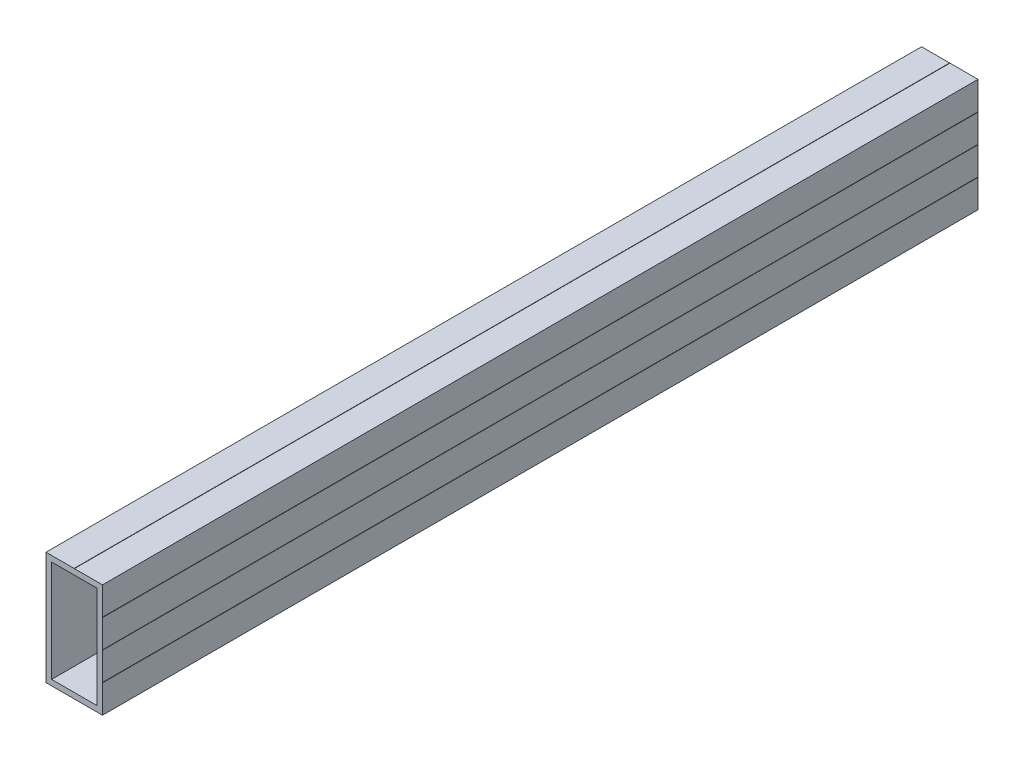
SolidWorks part; units mm, degrees
ref_plane "Front Plane" through (0, 0, 0) normal (0, 0, 1) x (1, 0, 0)
ref_plane "Top Plane" through (0, 0, 0) normal (0, 1, 0) x (1, 0, 0)
ref_plane "Right Plane" through (0, 0, 0) normal (1, 0, 0) x (0, 0, -1)
ref_plane "Plane1" through (12.7, 0, 0) normal (1, 0, 0) x (0, 0, -1)
sketch "Sketch1" plane through (12.7, 0, 0) normal (1, 0, 0) x (0, 0, -1)
  line L0 (-749.3, 25.4) -> (-749.3, -25.4)
  line L1 (-749.3, -25.4) -> (749.3, -25.4)
  line L2 (749.3, -25.4) -> (749.3, 25.4)
  line L3 (749.3, 25.4) -> (-749.3, 25.4)
extrude "Boss-Extrude1" add sketch "Sketch1" against normal blind 25.4
sketch "Sketch2" plane through (0, 0, 749.3) normal (0, 0, 1) x (1, 0, 0)
  line L0 (0.0762, 25.4) -> (-0.0762, 25.4)
  line L1 (-0.0762, 25.4) -> (0.0762, 25.2476)
  line L2 (0.0762, 25.2476) -> (0.0762, 25.4)
extrude "Cut-Extrude1" cut sketch "Sketch2" against normal blind 1498.6
sketch "Sketch3" plane through (0, 0, 749.3) normal (0, 0, 1) x (1, 0, 0)
  line L0 (12.7, 12.6238) -> (12.7, 12.7762)
  line L1 (12.7, 12.7762) -> (12.5476, 12.7762)
  line L2 (12.5476, 12.7762) -> (12.7, 12.6238)
extrude "Cut-Extrude2" cut sketch "Sketch3" against normal through all
sketch "Sketch4" plane through (0, 0, 749.3) normal (0, 0, 1) x (1, 0, 0)
  line L0 (12.7, -0.0762) -> (12.7, 0.0762)
  line L1 (12.7, 0.0762) -> (12.5476, -0.0762)
  line L2 (12.5476, -0.0762) -> (12.7, -0.0762)
extrude "Cut-Extrude3" cut sketch "Sketch4" against normal blind 1498.6
sketch "Sketch5" plane through (0, 0, 749.3) normal (0, 0, 1) x (1, 0, 0)
  line L0 (12.7, -12.7762) -> (12.7, -12.6238)
  line L1 (12.7, -12.6238) -> (12.5476, -12.6238)
  line L2 (12.5476, -12.6238) -> (12.7, -12.7762)
extrude "Cut-Extrude4" cut sketch "Sketch5" against normal blind 1498.6
sketch "Sketch6" plane through (0, 0, 749.3) normal (0, 0, 1) x (1, 0, 0)
  line L0 (0.0762, -25.4) -> (-0.0762, -25.2476)
  line L1 (-0.0762, -25.2476) -> (-0.0762, -25.4)
  line L2 (-0.0762, -25.4) -> (0.0762, -25.4)
extrude "Cut-Extrude5" cut sketch "Sketch6" against normal through all
sketch "Sketch7" plane through (0, 0, 749.3) normal (0, 0, 1) x (1, 0, 0)
  line L0 (-12.7, -12.6238) -> (-12.7, -12.7762)
  line L1 (-12.7, -12.7762) -> (-12.5476, -12.7762)
  line L2 (-12.5476, -12.7762) -> (-12.7, -12.6238)
extrude "Cut-Extrude6" cut sketch "Sketch7" against normal through all
sketch "Sketch8" plane through (0, 0, 749.3) normal (0, 0, 1) x (1, 0, 0)
  line L0 (-12.7, 0.0762) -> (-12.7, -0.0762)
  line L1 (-12.7, -0.0762) -> (-12.5476, 0.0762)
  line L2 (-12.5476, 0.0762) -> (-12.7, 0.0762)
extrude "Cut-Extrude7" cut sketch "Sketch8" against normal blind 1498.6
sketch "Sketch9" plane through (0, 0, 749.3) normal (0, 0, 1) x (1, 0, 0)
  line L0 (-12.7, 12.7762) -> (-12.7, 12.6238)
  line L1 (-12.7, 12.6238) -> (-12.5476, 12.6238)
  line L2 (-12.5476, 12.6238) -> (-12.7, 12.7762)
extrude "Cut-Extrude8" cut sketch "Sketch9" against normal blind 1498.6
sketch "Sketch10" plane through (0, 0, 749.3) normal (0, 0, 1) x (1, 0, 0)
  line L0 (10.16, -22.86) -> (10.16, 22.86)
  line L1 (10.16, 22.86) -> (-10.16, 22.86)
  line L2 (-10.16, 22.86) -> (-10.16, -22.86)
  line L3 (-10.16, -22.86) -> (10.16, -22.86)
extrude "Cut-Extrude9" cut sketch "Sketch10" against normal through all
draft "Draft1" type of draft neutral plane draft angle 45 faces to draft 1 face at (0.0762, 25.3238, 0) neutral plane through (-12.7, 25.4, -749.3) neutral plane normal (0, 1, 0) parameters "D1"=45
draft "Draft2" type of draft neutral plane draft angle 45 faces to draft 1 face at (12.6238, 12.7762, 0) neutral plane through (12.7, 0, 0) neutral plane normal (1, 0, 0) parameters "D1"=45
draft "Draft3" type of draft neutral plane draft angle 45 faces to draft 1 face at (-0.0762, -25.3238, 0) neutral plane through (-12.7, -25.4, 749.3) neutral plane normal (0, -1, 0) parameters "D1"=45
draft "Draft4" type of draft neutral plane draft angle 45 faces to draft 1 face at (-12.6238, -12.7762, 0) neutral plane through (-12.7, 0, 0) neutral plane normal (-1, 0, 0) parameters "D1"=45
draft "Draft5" type of draft neutral plane draft angle 45 faces to draft 2 face at (12.6238, -12.6238, 0) face at (12.6238, 0, 0) neutral plane through (12.7, 0, 0) neutral plane normal (1, 0, 0) parameters "D1"=45
draft "Draft6" type of draft neutral plane draft angle 45 faces to draft 2 face at (-12.6238, 0, 0) face at (-12.6238, 12.6238, 0) neutral plane through (-12.7, 0, 0) neutral plane normal (-1, 0, 0) parameters "D1"=45
sketch "Sketch11" plane through (0, 0, -749.3) normal (0, 0, -1) x (-1, 0, 0)
  line L1 (28.0564, 44.6652) -> (-33.9059, 44.6652)
  line L2 (28.0564, 44.6652) -> (28.0564, -44.0138)
  line L3 (28.0564, -44.0138) -> (-33.9059, -44.0138)
  line L4 (-33.9059, 44.6652) -> (-33.9059, -44.0138)
extrude "Cut-Extrude10" cut sketch "Sketch11" against normal blind 1104.9
